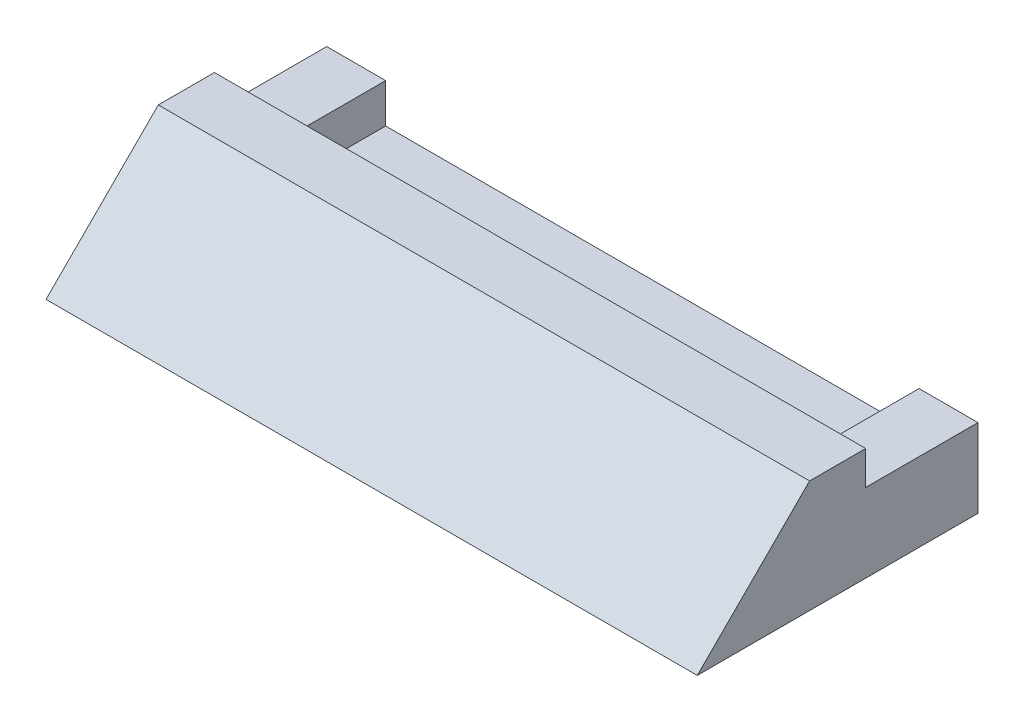
SolidWorks part; units mm, degrees
material "1060 Alloy"
ref_plane "Front Plane" through (0, 0, 0) normal (0, 0, 1) x (1, 0, 0)
ref_plane "Top Plane" through (0, 0, 0) normal (0, 1, 0) x (1, 0, 0)
ref_plane "Right Plane" through (0, 0, 0) normal (1, 0, 0) x (0, 0, -1)
sketch "Sketch1" plane through (0, 0, 0) normal (1, 0, 0) x (0, 0, -1)
  line L0 (0, 0) -> (10, 10)
  line L1 (10, 10) -> (25, 10)
  line L2 (25, 10) -> (25, 0)
  line L3 (25, 0) -> (0, 0)
  dimension "D1" = 45
  dimension "D2" = 10
  dimension "D3" = 15
extrude "Boss-Extrude1" add sketch "Sketch1" along normal blind 58
sketch "Sketch3" plane through (0, 10, 0) normal (0, 1, 0) x (1, 0, 0)
  line L0 (58, 25) -> (0, 25) construction
  line L1 (5.25, 25) -> (52.75, 25)
  line L2 (5.25, 25) -> (5.25, 15)
  line L3 (5.25, 15) -> (52.75, 15)
  line L4 (52.75, 25) -> (52.75, 15)
  line L5 (0, 25) -> (0, 10) construction
  line L6 (58, 25) -> (58, 10) construction
  dimension "D1" = 5.25
  dimension "D2" = 5.25
  dimension "D3" = 10
extrude "Cut-Extrude2" cut sketch "Sketch3" against normal blind 6.5
sketch "Sketch4" plane through (0, 3.5, 0) normal (0, 1, 0) x (1, 0, 0)
  line L0 (5.25, 15) -> (52.75, 15) construction
  line L1 (5.25, 25) -> (5.25, 15) construction
  line L3 (52.75, 15) -> (52.75, 25) construction
  line L4 (29, 25) -> (29, 20) construction
  line L5 (52.75, 25) -> (5.25, 25) construction
  circle A0 centre (10.25, 20) radius 1.5
  circle A1 centre (29, 20) radius 1.5
  circle A2 centre (47.75, 20) radius 1.5
  dimension "D1" = 3
  dimension "D2" = 5
  dimension "D3" = 5
  dimension "D5" = 5
extrude "Cut-Extrude3" cut sketch "Sketch4" against normal up to next
sketch "Sketch5" plane through (0, 10, 0) normal (0, 1, 0) x (1, 0, 0)
  line L0 (58, 25) -> (58, 10) construction
  line L1 (0, 25) -> (58, 25)
  line L2 (0, 25) -> (0, 15)
  line L3 (0, 15) -> (58, 15)
  line L4 (58, 25) -> (58, 15)
  line L5 (5.25, 15) -> (52.75, 15) construction
extrude "Cut-Extrude4" cut sketch "Sketch5" against normal offset from surface (3 mm away) 3.5 up to face at (47.75, 3.5, -18.5)
